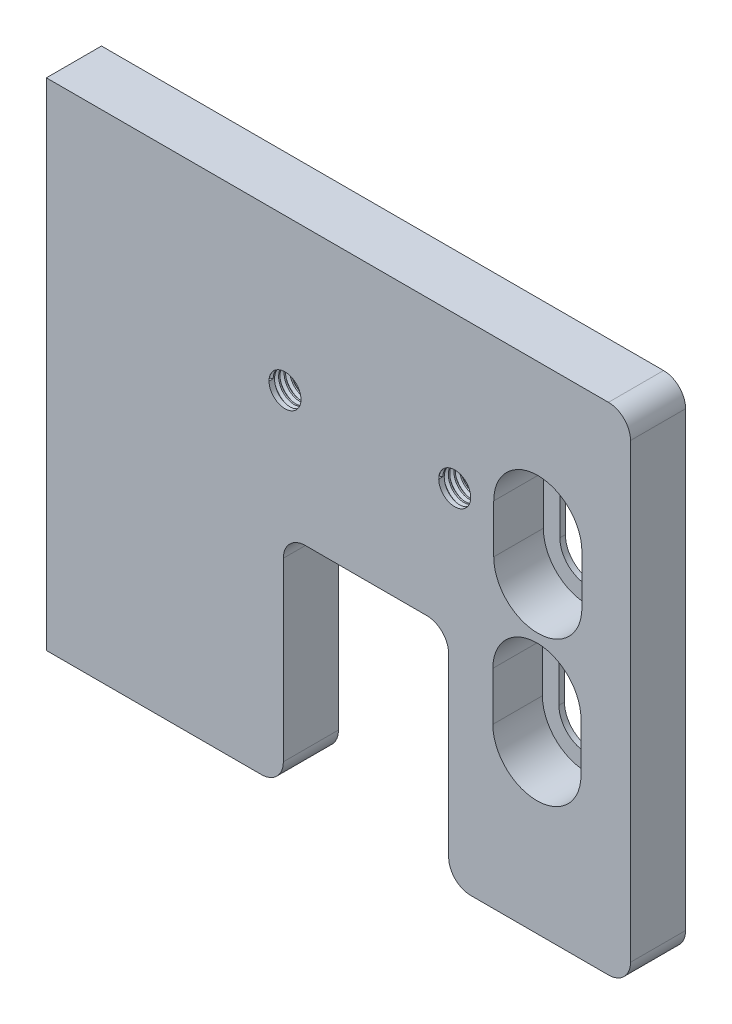
SolidWorks part; units mm, degrees
ref_plane "Front Plane" through (0, 0, 0) normal (0, 0, 1) x (1, 0, 0)
ref_plane "Top Plane" through (0, 0, 0) normal (0, 1, 0) x (1, 0, 0)
ref_plane "Right Plane" through (0, 0, 0) normal (1, 0, 0) x (0, 0, -1)
sketch "Sketch1" plane through (0, 0, 0) normal (0, 0, 1) x (1, 0, 0)
  line L0 (-34.2537, 0) -> (-34.2537, 45)
  line L1 (-34.2537, 45) -> (16.7463, 45)
  line L2 (18.7463, 43) -> (18.7463, 2)
  line L3 (16.7463, 0) -> (4.2463, 0)
  line L4 (2.2463, 2) -> (2.2463, 18)
  line L5 (0.2463, 20) -> (-10.7537, 20)
  line L6 (-12.7537, 18) -> (-12.7537, 2)
  line L7 (-14.7537, 0) -> (-34.2537, 0)
  arc A0 (16.7463, 45) -> (18.7463, 43) centre (16.7463, 43) cw
  arc A1 (18.7463, 2) -> (16.7463, 0) centre (16.7463, 2) cw
  arc A2 (4.2463, 0) -> (2.2463, 2) centre (4.2463, 2) cw
  arc A3 (-12.7537, 2) -> (-14.7537, 0) centre (-14.7537, 2) cw
  arc A4 (2.2463, 18) -> (0.2463, 20) centre (0.2463, 18) ccw
  arc A5 (-10.7537, 20) -> (-12.7537, 18) centre (-10.7537, 18) ccw
  point P11 (18.7463, 45)
  point P14 (18.7463, 0)
  point P17 (2.2463, 0)
  point P20 (-12.7537, 0)
  point P23 (2.2463, 20)
  point P26 (-12.7537, 20)
  dimension "D9" = 2
  dimension "D1" = 45
  dimension "D2" = 53
  dimension "D3" = 16.5
  dimension "D4" = 20
  dimension "D5" = 15
  dimension "D6" = 20
  dimension "D7" = 21.5
  dimension "D8" = 45
extrude "Boss-Extrude1" add sketch "Sketch1" along normal blind 5
sketch "Sketch19" plane through (0, 0, 5) normal (0, 0, 1) x (1, 0, 0)
  line L4 (6.3371, 27.65) -> (6.3371, 32.05)
  line L5 (14.3371, 32.05) -> (14.3371, 27.65)
  line L10 (6.2547, 18.85) -> (6.2547, 14.45)
  line L11 (14.2538, 18.7668) -> (14.2538, 14.45)
  arc A0 (6.3371, 32.05) -> (14.3371, 32.05) centre (10.3371, 32.05) cw
  arc A3 (6.3371, 27.65) -> (14.3371, 27.65) centre (10.3371, 27.65) ccw
  arc A7 (6.2547, 18.85) -> (14.2538, 18.7668) centre (10.2547, 18.85) cw
  arc A8 (6.2547, 14.45) -> (14.2538, 14.45) centre (10.2543, 14.45) ccw
  dimension "D1" = 4
  dimension "D2" = 8
  dimension "D3" = 4
extrude "Cut-Extrude6" cut sketch "Sketch19" against normal blind 4.5
sketch "Sketch20" plane through (0, 0, 0.5) normal (0, 0, 1) x (1, 0, 0)
  line L0 (7.7543, 14.45) -> (12.7543, 14.45) construction
  line L1 (7.7547, 18.85) -> (12.7547, 18.85) construction
  line L2 (7.7547, 18.85) -> (7.7543, 14.45)
  line L3 (12.7547, 18.85) -> (12.7543, 14.45)
  line L4 (7.8371, 32.05) -> (7.8371, 27.65)
  line L5 (12.8371, 32.05) -> (12.8371, 27.65)
  line L6 (4.2463, 0) -> (16.7463, 0) construction
  line L7 (18.7463, 2) -> (18.7463, 43) construction
  line L8 (16.7463, 45) -> (-34.2537, 45) construction
  arc A0 (7.7543, 14.45) -> (12.7543, 14.45) centre (10.2543, 14.45) ccw
  arc A1 (12.7547, 18.85) -> (7.7547, 18.85) centre (10.2547, 18.85) ccw
  arc A2 (12.8371, 32.05) -> (7.8371, 32.05) centre (10.3371, 32.05) ccw
  arc A3 (7.8371, 27.65) -> (12.8371, 27.65) centre (10.3371, 27.65) ccw
  point P18 (10.2543, 16.65)
  point P19 (10.3371, 29.4462)
  dimension "D1" = 5
  dimension "D2" = 5
  dimension "D3" = 5
  dimension "D4" = 5
  dimension "D5" = 16.65
  dimension "D6" = 8.492
  dimension "D7" = 15.5538
  dimension "D8" = 8.4092
extrude "Cut-Extrude7" cut sketch "Sketch20" against normal through all contours L4 A3 L5 A2 | L3 A1 L2 A0 region at (10.2545, 16.65, 0.5) region at (10.3371, 29.85, 0.5)
sketch "Sketch21" plane through (0, 0, 5) normal (0, 0, 1) x (1, 0, 0)
  line L0 (18.7463, 31.8) -> (4.1463, 31.8) construction
  line L1 (18.7463, 2) -> (18.7463, 43) construction
  line L2 (16.7463, 45) -> (-34.2537, 45) construction
  line L3 (-34.2537, 45) -> (-34.2537, 0) construction
  line L4 (1.3463, 31.2708) -> (-11.1537, 31.2708) construction
  circle A0 centre (2.7963, 31.2708) radius 1.45
  circle A1 centre (-12.6037, 31.2708) radius 1.45
  point P8 (1.3463, 31.2708)
  dimension "D3" = 2.9
  dimension "D6" = 2.9
  dimension "D1" = 14.6
  dimension "D2" = 13.2
  dimension "D4" = 35.6
  dimension "D5" = 12.5
extrude "Cut-Extrude8" cut sketch "Sketch21" against normal blind 4.5
thread "Thread1" pitch 0.5 method cut profile "Thread Profile1" start angle 0, offset 0, length 0, pitch 0.5, diameter 2.9
ref_plane "Plane1" through (-14.0537, 31.2708, 5) normal (0, -1, 0) x (-1, 0, 0)
sketch "Thread Profile1" plane through (-14.0537, 31.2708, 5) normal (0, -1, 0) x (-1, 0, 0)
  line L0 (0, 0) -> (0, 0.5) construction
  line L1 (0, 0) -> (0.2706, 0.1562)
  line L2 (0.2706, 0.1562) -> (0.2706, 0.2187)
  line L3 (0.2706, 0.2187) -> (0, 0.375)
  line L4 (0.2706, 0.1875) -> (0, 0.1875) construction
  line L11 (0, 0) -> (0, 0.375)
  point P2 (0, 0)
  dimension "Pitch" = 0.5
  dimension "Profile_Angle" = 60
  dimension "Profile_Land" = 0.0625
  dimension "Profile_Height" = 0.2706
thread "Thread2" pitch 0.5 method cut profile "Thread Profile2" start angle 0, offset 0, length 0, pitch 0.5, diameter 2.9
ref_plane "Plane2" through (1.3463, 31.2708, 5) normal (0, -1, 0) x (-1, 0, 0)
sketch "Thread Profile2" plane through (1.3463, 31.2708, 5) normal (0, -1, 0) x (-1, 0, 0)
  line L0 (0, 0) -> (0, 0.5) construction
  line L1 (0, 0) -> (0.2706, 0.1562)
  line L2 (0.2706, 0.1562) -> (0.2706, 0.2187)
  line L3 (0.2706, 0.2187) -> (0, 0.375)
  line L4 (0.2706, 0.1875) -> (0, 0.1875) construction
  line L11 (0, 0) -> (0, 0.375)
  point P2 (0, 0)
  dimension "Pitch" = 0.5
  dimension "Profile_Angle" = 60
  dimension "Profile_Land" = 0.0625
  dimension "Profile_Height" = 0.2706
